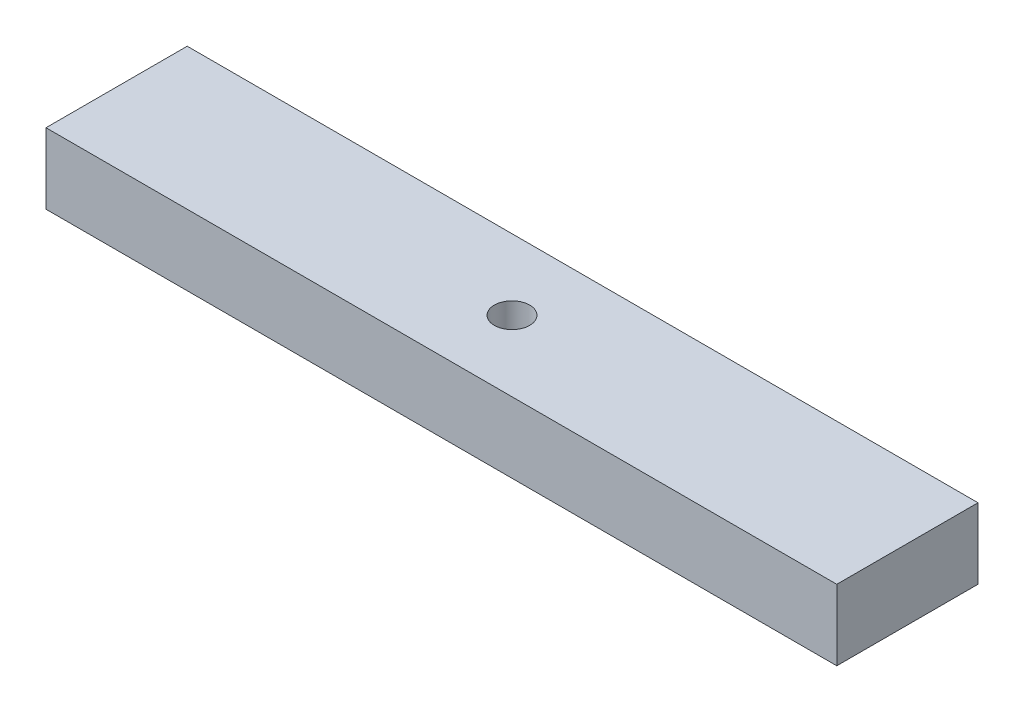
SolidWorks part; units mm, degrees
ref_plane "Front Plane" through (0, 0, 0) normal (0, 0, 1) x (1, 0, 0)
ref_plane "Top Plane" through (0, 0, 0) normal (0, 1, 0) x (1, 0, 0)
ref_plane "Right Plane" through (0, 0, 0) normal (1, 0, 0) x (0, 0, -1)
sketch "Sketch1" plane through (0, 0, 0) normal (0, 1, 0) x (1, 0, 0)
  line L1 (0, 0) -> (142.24, 0)
  line L2 (0, 0) -> (0, 25.4)
  line L3 (0, 25.4) -> (142.24, 25.4)
  line L4 (142.24, 0) -> (142.24, 25.4)
  circle A0 centre (71.12, 12.7) radius 3.175
  dimension "D3" = 6.35
  dimension "D4" = 12.7
  dimension "D1" = 142.24
  dimension "D2" = 25.4
  dimension "D5" = 71.12
extrude "Boss-Extrude1" add sketch "Sketch1" along normal blind 12.7
